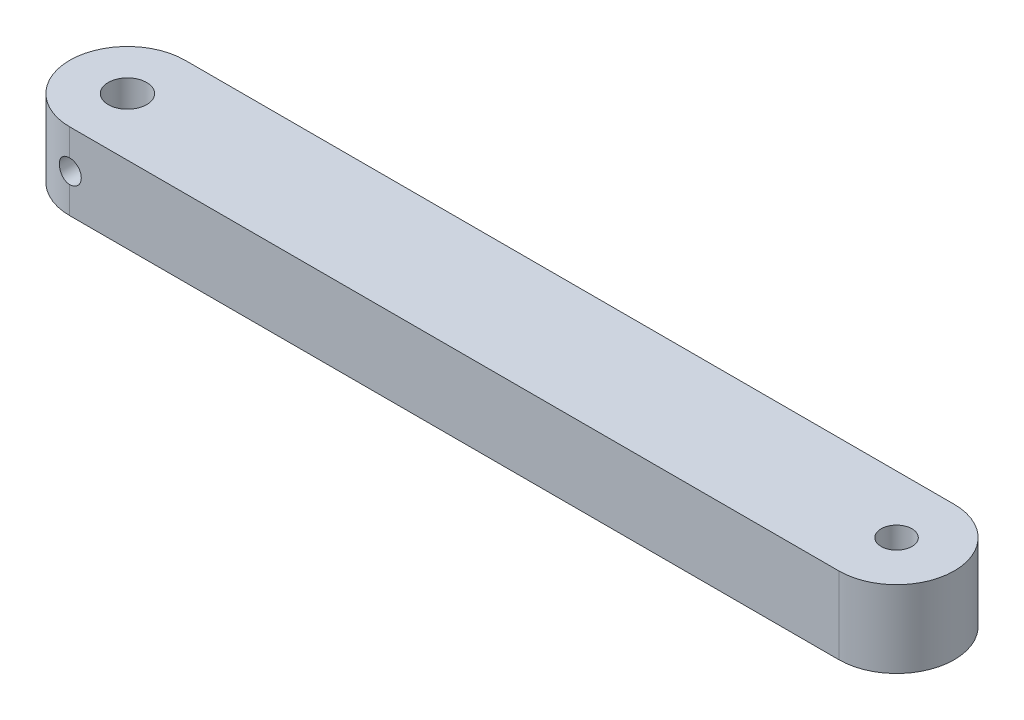
SolidWorks part; units mm, degrees
ref_plane "Front Plane" through (0, 0, 0) normal (0, 0, 1) x (1, 0, 0)
ref_plane "Top Plane" through (0, 0, 0) normal (0, 1, 0) x (1, 0, 0)
ref_plane "Right Plane" through (0, 0, 0) normal (1, 0, 0) x (0, 0, -1)
sketch "Sketch2" plane through (0, 0, 0) normal (0, 1, 0) x (1, 0, 0)
  line L0 (0, 0) -> (100, 0) construction
  line L1 (0, 7.5) -> (100, 7.5)
  line L2 (0, -7.5) -> (100, -7.5)
  arc A0 (0, 7.5) -> (0, -7.5) centre (0, 0) ccw
  arc A1 (100, -7.5) -> (100, 7.5) centre (100, 0) ccw
  circle A2 centre (0, 0) radius 2.5
  circle A3 centre (100, 0) radius 2
  point P3 (50, 0)
  dimension "D2" = 5
  dimension "D4" = 4
  dimension "D1" = 100
  dimension "D3" = 15
extrude "Boss-Extrude1" add sketch "Sketch2" along normal blind 10
sketch "Sketch4" plane through (0, 0, -7.5) normal (0, 0, -1) x (-1, 0, 0)
  line L0 (0, 10) -> (0, 0) construction
  circle A0 centre (0, 5) radius 1.5
extrude "Cut-Extrude3" cut sketch "Sketch4" against normal through all
sketch "Sketch5" plane through (0, 10, 0) normal (0, 1, 0) x (1, 0, 0)
  line L1 (100, 7.5) -> (0, 7.5) construction
  line L2 (114.9191, 7.5) -> (100, 7.5)
  line L4 (0, -7.5) -> (100, -7.5) construction
  line L5 (115.1207, -7.5) -> (100, -7.5)
  line L6 (112.5, -7.5) -> (112.5, 7.5)
  line L7 (112.5, 7.5) -> (114.9191, 7.5)
  line L9 (112.5, -7.5) -> (115.1207, -7.5)
  arc A0 (100, -7.5) -> (100, 7.5) centre (100, 0) ccw
extrude "Cut-Extrude5" [suppressed] cut sketch "Sketch5" against normal blind 3
sketch "Sketch6" [suppressed] plane through (0, 10, 0) normal (0, 1, 0) x (1, 0, 0)
  line L1 (112.5, 7.5) -> (120, 7.5)
  line L2 (120, -7.5) -> (112.5, -7.5)
  line L5 (112.5, 7.5) -> (112.5, -7.5) construction
  line L6 (112.5, 7.5) -> (112.5, -7.5)
  arc A1 (120, 7.5) -> (127.5, 0) centre (120, 0) cw
  arc A2 (120, -7.5) -> (120, 7.5) centre (120, 0) ccw construction
  arc A3 (127.5, 0) -> (120, -7.5) centre (120, 0) cw
extrude "Cut-Extrude6" [suppressed] cut sketch "Sketch6" against normal up to next from offset 7 offset against normal yes
